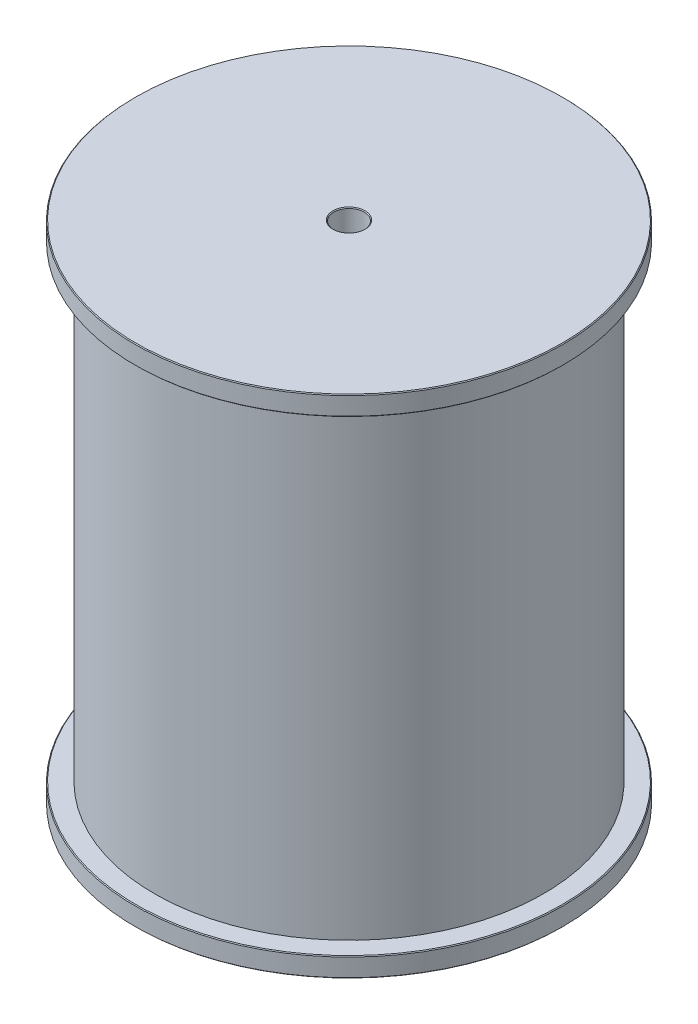
SolidWorks part; units mm, degrees
material "6061-T6 (SS)"
ref_plane "Front Plane" through (0, 0, 0) normal (0, 0, 1) x (1, 0, 0)
ref_plane "Top Plane" through (0, 0, 0) normal (0, 1, 0) x (1, 0, 0)
ref_plane "Right Plane" through (0, 0, 0) normal (1, 0, 0) x (0, 0, -1)
sketch "Sketch1" plane through (0, 0, 0) normal (0, 0, 1) x (1, 0, 0)
  line L0 (2.4892, 0) -> (34.925, 0)
  line L1 (34.925, 0) -> (34.925, 3.175)
  line L2 (34.925, 3.175) -> (31.75, 3.175)
  line L3 (31.75, 3.175) -> (31.75, 79.375)
  line L4 (31.75, 79.375) -> (34.925, 79.375)
  line L5 (34.925, 79.375) -> (34.925, 82.55)
  line L6 (34.925, 82.55) -> (2.4892, 82.55)
  line L7 (0, 82.55) -> (0, 0) construction
  line L8 (2.4892, 0) -> (2.4892, 41.275)
  line L10 (2.4892, 4.7752) -> (2.4892, 36.4998)
  line L12 (2.4892, 41.275) -> (2.4892, 82.55)
  line L13 (2.4892, 82.55) -> (0, 82.55) construction
  line L14 (0, 0) -> (2.4892, 0) construction
  point P14 (2.4892, 41.7665)
  dimension "D1" = 63.5
  dimension "D2" = 69.85
  dimension "D3" = 76.2
  dimension "D4" = 82.55
  dimension "D5" = 4.9784
  dimension "D7" = 4.9784
revolve "Revolve1" add sketch "Sketch1" angle 360 about L7 region at (17.2538, 41.275, 0)
chamfer "Chamfer1" distance 0.127 angle 45 6 edges at (-34.925, 79.375, 0) (-34.925, 3.175, 0) (-2.4892, 0, 0) (-34.925, 0, 0) (-34.925, 82.55, 0) (-2.4892, 82.55, 0)
